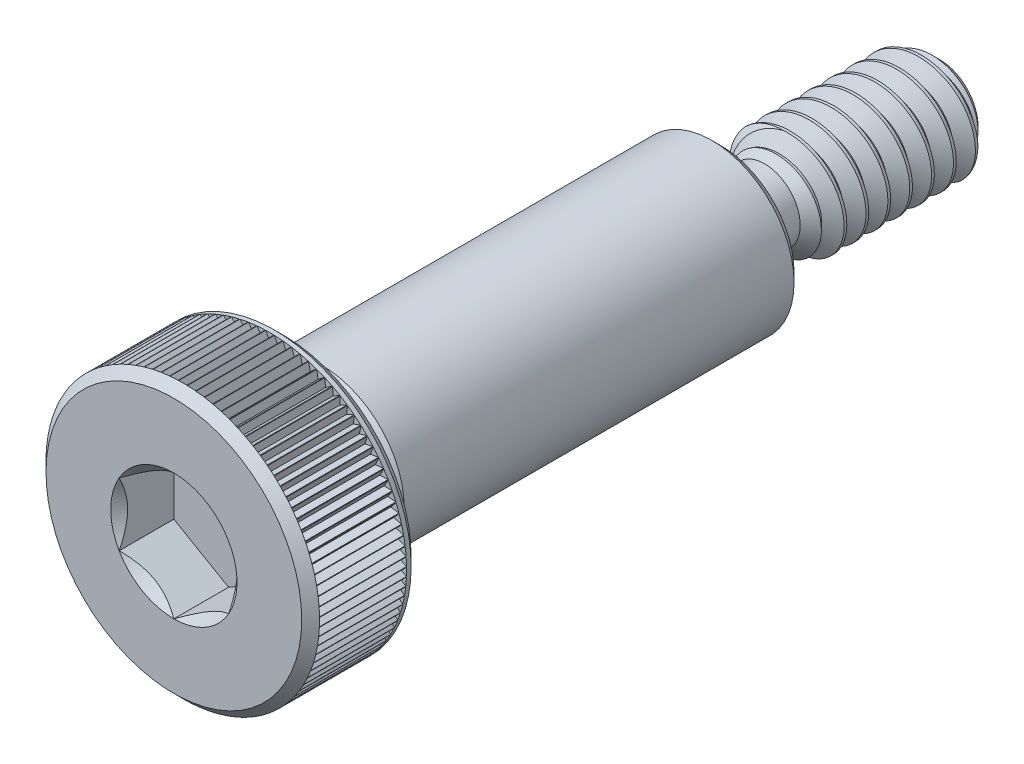
SolidWorks part; units mm, degrees
ref_plane "Front Plane" through (0, 0, 0) normal (0, 0, 1) x (1, 0, 0)
ref_plane "Top Plane" through (0, 0, 0) normal (0, 1, 0) x (1, 0, 0)
ref_plane "Right Plane" through (0, 0, 0) normal (1, 0, 0) x (0, 0, -1)
sketch "Sketch1" plane through (0, 0, 0) normal (1, 0, 0) x (0, 0, -1)
  line L0 (-7, 0) -> (7, 0) construction
  line L1 (-7, -2.5) -> (-7, 2.5) construction
  line L2 (-7, 2.5) -> (-5, 2.5) construction
  line L3 (-5, 2.5) -> (-5, 1.297) construction
  line L4 (-5, 1.297) -> (-4.492, 1.297) construction
  line L5 (-4.492, 1.297) -> (-4.289, 1.5) construction
  line L6 (-4.289, 1.5) -> (3, 1.5) construction
  line L7 (6.975, 1.0433) -> (7.175, 0.6969) construction
  line L8 (7.175, 0.6969) -> (7.375, 1.0433) construction
  line L9 (7, -1) -> (7, 1) construction
  line L10 (3, 1.5) -> (7, 1.5) construction
  line L11 (7.375, 1.0433) -> (6.975, 1.0433) construction
  line L12 (7.175, 1.0433) -> (7.175, 1) construction
  line L13 (7.175, 0.6969) -> (7.175, 0.7402) construction
  line L14 (7.2, 0.7402) -> (7.15, 0.7402) construction
  line L15 (7.35, 1) -> (7, 1) construction
  line L16 (7.175, 1.0217) -> (7.3625, 1.0217) construction
  line L17 (7.175, 1.0217) -> (6.9875, 1.0217) construction
  line L18 (-7, 2.3375) -> (-6.8375, 2.5) construction
  line L19 (-5.1625, 2.5) -> (-5, 2.3375) construction
  line L20 (7, 1) -> (3, 1) construction
  line L21 (6.7, 1) -> (7, 0.7) construction
  line L22 (4.15, 1) -> (3.8, 0.65) construction
  line L23 (3.8, 0.65) -> (3.175, 0.65) construction
  line L24 (3, 1) -> (3, 0.825) construction
  line L25 (-6, 1) -> (-6, -1) construction
  line L26 (-6, -1) -> (-7, -1) construction
  line L27 (-6, 1) -> (-7, 1) construction
  line L28 (-6.8375, 0) -> (-5.2463, 0) construction
  arc A0 (3, 0.825) -> (3.175, 0.65) centre (3.175, 0.825) ccw construction
  point P4 (0, 0)
  point P7 (-7, 0)
  point P18 (7, 0)
  point P25 (5.6, -1)
  point P38 (-6, 2.5)
  point P45 (-6, 0)
  point P46 (3.975, 0.825)
  point P48 (-4.492, 0)
  point P51 (-6, 0)
  point P52 (3, 0)
  dimension "Head Diameter" = 5
  dimension "Head Height" = 2
  dimension "Thread Diameter" = 2
  dimension "Shoulder Diameter" = 3
  dimension "Thread Length" = 4
  dimension "D1" = 0.508
  dimension "D2" = 135
  dimension "D3" = 0.203
  dimension "Shoulder Length" = 8
  dimension "Thread Pitch" = 0.4
  dimension "D4" = 0.05
  dimension "D5" = 1.4
  dimension "D6" = 0.1625
  dimension "D7" = 0.3
  dimension "D8" = 1.3
  dimension "D9" = 0.8
  dimension "Drive Size" = 2
  dimension "Knurling Length" = 1.5913
sketch "Sketch3" plane through (0, 0, 0) normal (1, 0, 0) x (0, 0, -1)
  line L0 (-7, 0) -> (-7, 2.3375)
  line L1 (-7, -2.5) -> (-7, 2.5) construction
  line L2 (-7, 2.3375) -> (-6.8375, 2.5)
  line L3 (-6.8375, 2.5) -> (-5.1625, 2.5)
  line L4 (-5.1625, 2.5) -> (-5, 2.3375)
  line L5 (-5, 2.3375) -> (-5, 1.297)
  line L6 (-5, 1.297) -> (-4.492, 1.297)
  line L7 (-4.492, 1.297) -> (-4.289, 1.5)
  line L8 (-4.289, 1.5) -> (3, 1.5)
  line L9 (3, 1.5) -> (3, 0.825)
  line L10 (3.175, 0.65) -> (3.8, 0.65)
  line L11 (3.8, 0.65) -> (4.15, 1)
  line L12 (4.15, 1) -> (6.7, 1)
  line L13 (6.7, 1) -> (7, 0.7)
  line L14 (7, 0.7) -> (7, 0)
  line L15 (7, 0) -> (-7, 0)
  arc A0 (3, 0.825) -> (3.175, 0.65) centre (3.175, 0.825) ccw construction
  arc A1 (3, 0.825) -> (3.175, 0.65) centre (3.175, 0.825) ccw
revolve "Revolve1" add sketch "Sketch3" angle 360 about L0
sketch "Sketch4" plane through (0, 0, 0) normal (0, 0, 1) x (1, 0, 0)
  line L0 (0, -2.5) -> (0, 2.5) construction
  line L1 (0, 1.1547) -> (-1, 0.5774)
  line L2 (-1, 0.5774) -> (-1, -0.5774)
  line L3 (-1, -0.5774) -> (0, -1.1547)
  line L4 (0, -1.1547) -> (1, -0.5774)
  line L5 (1, -0.5774) -> (1, 0.5774)
  line L6 (1, 0.5774) -> (0, 1.1547)
  circle A0 centre (0, 0) radius 1 construction
extrude "Cut-Extrude1" cut sketch "Sketch4" against normal up to vertex (-6 mm away) from vertex up to point (0, 0, 6) starting at point (0, 0, 7)
sketch "Sketch5" plane through (0, 0, 0) normal (0, 0, 1) x (1, 0, 0)
  line L0 (0, -2.5) -> (0, 2.5) construction
  circle A0 centre (0, 0) radius 1.1547
extrude "Cut-Extrude2" cut sketch "Sketch5" against normal up to vertex (-6 mm away) draft 45 from vertex up to point (0, 0, 6) starting at point (0, 0, 7)
chamfer "Chamfer1" distance 0.1625 angle 45 1 edges at (1.5, 0, -3)
sketch "Sketch6" plane through (0, 0, -7) normal (0, 0, -1) x (-1, 0, 0)
  circle A0 centre (0, 0) radius 1
curve "Helix/Spiral1" pitch 0.4 height 3.8 radius 1 centre (0, 0, -7) axis (0, 0, 1) start towards (0, 1, 0)
sketch "Sketch7" plane through (0, 0, 0) normal (1, 0, 0) x (0, 0, -1)
  line L0 (6.9875, 1.0217) -> (7.15, 0.7402)
  line L1 (7.15, 0.7402) -> (7.2, 0.7402)
  line L2 (7.2, 0.7402) -> (7.3625, 1.0217)
  line L3 (7.3625, 1.0217) -> (6.9875, 1.0217)
sweep "Cut-Sweep1" cut profiles "Sketch7" path "Helix/Spiral1"
sketch "Sketch8" plane through (0, 0, 0) normal (0, 0, 1) x (1, 0, 0)
  line L0 (0, 2.5) -> (0, 0) construction
  line L1 (-0.0751, 2.5) -> (0.0751, 2.5)
  line L2 (0.0751, 2.5) -> (0, 2.37)
  line L3 (0, 2.37) -> (-0.0751, 2.5)
  line L4 (-0.0751, 2.5) -> (0, 0) construction
  line L5 (0, 0) -> (0.0751, 2.5) construction
  circle A0 centre (0, 0) radius 2.37 construction
  point P8 (0, 2.5)
  dimension "D1" = 0.13
  dimension "D2" = 3.439
extrude "Cut-Extrude3" cut sketch "Sketch8" against normal up to vertex (-5.2462 mm away) from vertex up to point (0, 0, 5.2463) starting at point (0, 0, 6.8375)
pattern_circular "CirPattern1" count 99 over 360 about axis through (0, 0, 7) along (0, 0, -1) of "Cut-Extrude3"
equation "\"D4@Sketch1\"=\"Thread Pitch@Sketch1\"/8"
equation "\"D5@Sketch1\"=\"Thread Pitch@Sketch1\"*3.5"
equation "\"D6@Sketch1\"=\"Head Diameter@Sketch1\"*.0325"
equation "\"D7@Sketch1\"=\"Thread Pitch@Sketch1\"*.75"
equation "\"D8@Sketch1\"=\"Thread Diameter@Sketch1\"*.65"
equation "\"D9@Sketch1\"=\"Thread Length@Sketch1\"*.2"
equation "\"D1@Chamfer1\"=\"D6@Sketch1\""
equation "\"D4@Helix/Spiral1\"=\"Thread Pitch@Sketch1\""
equation "\"D3@Helix/Spiral1\"=\"Thread Length@Sketch1\"*.95"
equation "\"D1@Sketch8\"=\"D6@Sketch1\"*.8"
equation "\"D1@CirPattern1\"=(360/\"D2@Sketch8\")-6"
equation "\"D1@Cut-Extrude3\"=\"D11@Sketch1\""
